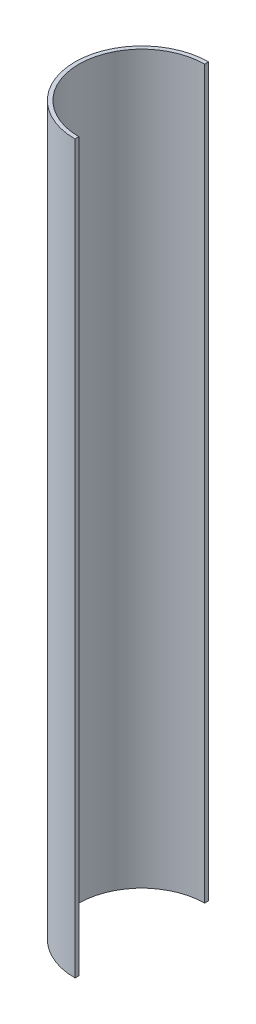
SolidWorks part; units mm, degrees
ref_plane "Front Plane" through (0, 0, 0) normal (0, 0, 1) x (1, 0, 0)
ref_plane "Top Plane" through (0, 0, 0) normal (0, 1, 0) x (1, 0, 0)
ref_plane "Right Plane" through (0, 0, 0) normal (1, 0, 0) x (0, 0, -1)
sketch "Sketch1" plane through (0, 0, 0) normal (0, 1, 0) x (1, 0, 0)
  line L1 (0, 107.95) -> (0, 101.6)
  line L2 (0, -101.6) -> (0, -107.95)
  arc A1 (0, 101.6) -> (0, -101.6) centre (0, 0) ccw
  arc A2 (0, 107.95) -> (0, -107.95) centre (0, 0) ccw
  dimension "D1" = 101.6
  dimension "D2" = 6.35
  dimension "D3" = 107.95
  dimension "D4" = 6.35
extrude "Boss-Extrude1" add sketch "Sketch1" along normal blind 1174.75
